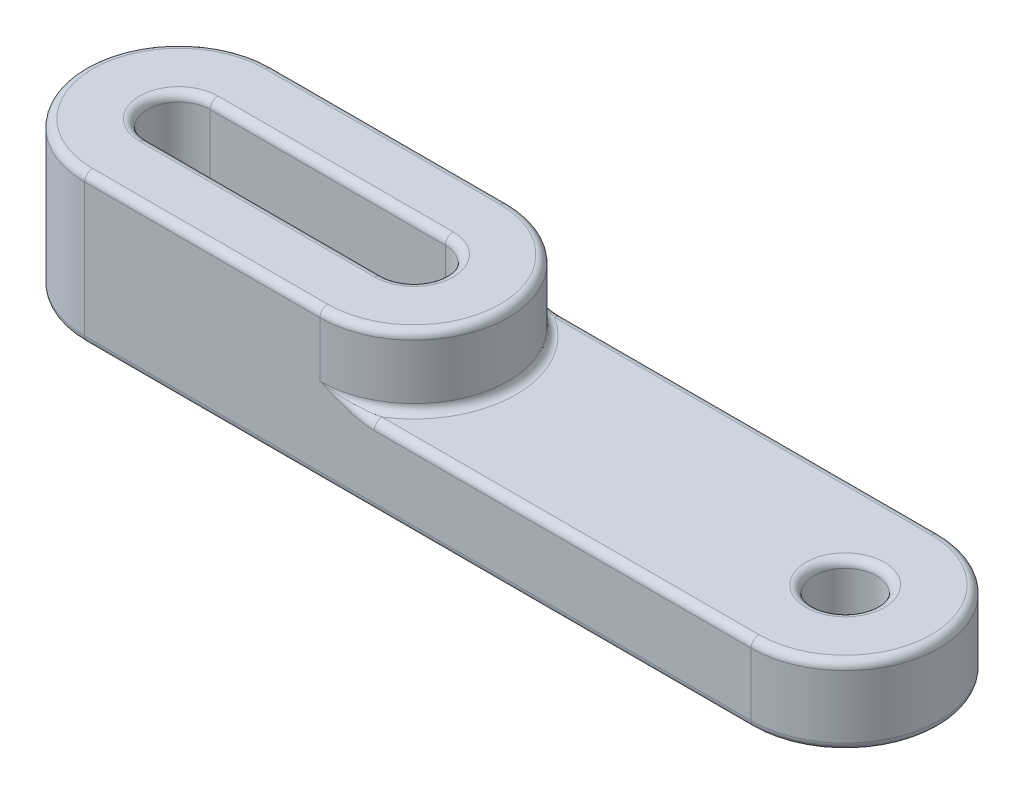
SolidWorks part; units mm, degrees
ref_plane "Front Plane" through (0, 0, 0) normal (0, 0, 1) x (1, 0, 0)
ref_plane "Top Plane" through (0, 0, 0) normal (0, 1, 0) x (1, 0, 0)
ref_plane "Right Plane" through (0, 0, 0) normal (1, 0, 0) x (0, 0, -1)
sketch "Sketch2" plane through (0, 0, 0) normal (0, 1, 0) x (1, 0, 0)
  line L0 (0, 0) -> (30, 0) construction
  line L1 (0, 4) -> (30, 4)
  line L2 (0, -4) -> (30, -4)
  line L3 (0, 0) -> (85, 0) construction
  line L4 (0, 12) -> (85, 12)
  line L5 (0, -12) -> (85, -12)
  line L6 (89, 0) -> (97, 0) construction
  arc A0 (0, 4) -> (0, -4) centre (0, 0) ccw
  arc A1 (30, -4) -> (30, 4) centre (30, 0) ccw
  circle A2 centre (85, 0) radius 4
  arc A3 (0, 12) -> (0, -12) centre (0, 0) ccw
  arc A4 (85, -12) -> (85, 12) centre (85, 0) ccw
  point P3 (15, 0)
  point P12 (42.5, 0)
  point P17 (-4, 0)
  point P18 (-12, 0)
  dimension "D4" = 8
  dimension "D1" = 8
  dimension "D2" = 30
  dimension "D3" = 55
  dimension "D5" = 8
  dimension "D6" = 8
  dimension "D7" = 8
extrude "Boss-Extrude1" add sketch "Sketch2" along normal blind 10
sketch "Sketch3" plane through (0, 10, 0) normal (0, 1, 0) x (1, 0, 0)
  line L0 (0, 0) -> (30, 0) construction
  line L1 (0, 12) -> (30, 12)
  line L2 (0, -12) -> (30, -12)
  line L3 (0, 0) -> (30, 0) construction
  line L4 (34, 0) -> (42, 0) construction
  line L5 (0, 4) -> (30, 4)
  line L6 (0, -4) -> (30, -4)
  arc A0 (0, 12) -> (0, -12) centre (0, 0) ccw
  arc A1 (30, -12) -> (30, 12) centre (30, 0) ccw
  arc A3 (30, -4) -> (30, 4) centre (30, 0) ccw construction
  arc A4 (0, 4) -> (0, -4) centre (0, 0) ccw
  arc A5 (30, -4) -> (30, 4) centre (30, 0) ccw
  point P3 (15, 0)
  point P10 (15, 0)
  dimension "D1" = 12
  dimension "D2" = 0
  dimension "D3" = 8
  dimension "D4" = 8
extrude "Boss-Extrude2" add sketch "Sketch3" along normal blind 9
fillet "Fillet1" radius 1 22 edges at (57.5, 10, -12) (97, 10, 0) (57.5, 10, 12) (42.5, 0, -12) (97, 0, 0) (42.5, 0, 12) (-12, 0, 0) (15, 0, -4) (34, 0, 0) (15, 0, 4) (-4, 0, 0) (85, 10, 4) (85, 0, 4) (15, 19, -12) (42, 19, 0) (15, 19, 12) (-12, 19, 0) (42, 10, 0) (15, 19, -4) (34, 19, 0) (15, 19, 4) (-4, 19, 0)
